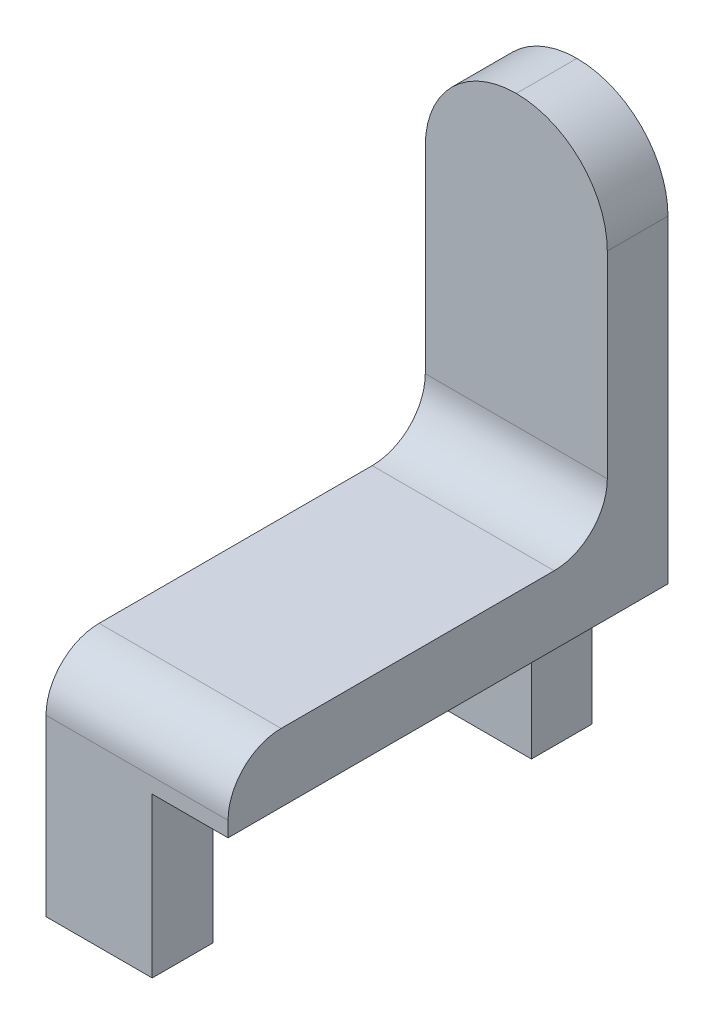
SolidWorks part; units mm, degrees
ref_plane "Front Plane" through (0, 0, 0) normal (0, 0, 1) x (1, 0, 0)
ref_plane "Top Plane" through (0, 0, 0) normal (0, 1, 0) x (1, 0, 0)
ref_plane "Right Plane" through (0, 0, 0) normal (1, 0, 0) x (0, 0, -1)
sketch "Sketch2" plane through (0, -0.0002, -27.9978) normal (0, 0, -1) x (1, 0, 0)
  line L1 (45.1952, -27.127) -> (69.1952, -27.127)
  line L2 (45.1952, -27.127) -> (45.1952, 47.873)
  line L3 (45.1952, 47.873) -> (69.1952, 47.873)
  line L4 (69.1952, -27.127) -> (69.1952, 47.873)
  dimension "D4" = 75
extrude "Boss-Extrude1" add sketch "Sketch2" along normal blind 8
fillet "Fillet1" radius 12 2 edges at (45.1952, 27.1268, -31.9981) (69.1952, 27.1268, -31.9981)
sketch "Sketch3" plane through (0, -0.0002, -27.9978) normal (0, 0, 1) x (1, 0, 0)
  line L0 (69.1952, 15.127) -> (69.1952, -47.873) construction
  line L1 (45.1952, -47.873) -> (69.1952, -47.873)
  line L2 (45.1952, -47.873) -> (45.1952, -17.873)
  line L3 (45.1952, -17.873) -> (69.1952, -17.873)
  line L4 (69.1952, -47.873) -> (69.1952, -17.873)
  dimension "D1" = 30
extrude "Boss-Extrude2" add sketch "Sketch3" along normal blind 50
sketch "Sketch4" plane through (69.1952, 0, 0) normal (1, 0, 0) x (0, 0, -1)
  line L2 (27.9977, -54.1007) -> (27.9977, -26.8732)
  line L3 (27.9977, -26.8732) -> (-14.0023, -26.8732)
  line L4 (-14.0023, -54.1007) -> (-14.0023, -26.8732)
  line L5 (-22.0023, -17.8728) -> (35.9977, -17.8728) construction
  line L6 (35.998, 15.1267) -> (35.9975, -47.8733) construction
  line L7 (6.9977, -17.8728) -> (6.9977, -54.1007) construction
  line L8 (27.9977, -54.1007) -> (-14.0023, -54.1007)
  dimension "D1" = 21
  dimension "D2" = 42
extrude "Cut-Extrude1" cut sketch "Sketch4" against normal up to surface (24 mm away) up to face at (45.1952, -16.8731, -13.9977)
fillet "Fillet2" radius 7 2 edges at (57.1952, -17.8728, 22.0023) (57.1952, -17.8732, -27.9977)
sketch "Sketch5" plane through (69.1952, 0, 0) normal (1, 0, 0) x (0, 0, -1)
  line L10 (-22.0025, -47.8728) -> (-22.0024, -24.8728) construction
  line L11 (35.998, 15.1267) -> (35.9975, -47.8733) construction
  line L20 (20.9977, -17.8732) -> (-15.0023, -17.8729)
  line L21 (-22.0024, -24.8728) -> (-22.0025, -47.8728)
  line L22 (-22.0025, -47.8728) -> (-14.0023, -47.8729)
  line L23 (-14.0023, -47.8729) -> (-14.0023, -26.8732)
  line L24 (-14.0023, -26.8732) -> (27.9977, -26.8732)
  line L25 (27.9977, -26.8732) -> (27.9977, -47.8732)
  line L26 (27.9977, -47.8732) -> (35.9975, -47.8733)
  line L27 (35.9975, -47.8733) -> (35.998, 15.1267)
  line L28 (35.998, 15.1267) -> (27.998, 15.1268)
  line L29 (27.998, 15.1268) -> (27.9978, -10.8732)
  line L31 (-22.0024, -26.8732) -> (-22.0025, -47.8728)
  line L32 (-22.0025, -47.8728) -> (35.9975, -47.8733)
  line L34 (-22.0024, -26.8732) -> (35.9976, -26.8732)
  line L37 (35.9975, -47.8733) -> (35.9976, -26.8732)
  arc A2 (-15.0023, -17.8729) -> (-22.0024, -24.8728) centre (-15.0024, -24.8729) ccw
  arc A3 (20.9977, -17.8732) -> (27.9978, -10.8732) centre (20.9978, -10.8732) ccw
  point P2 (0, 0)
  point P8 (35.479, -47.8733)
  point P9 (-22.0024, -26.8732)
  point P18 (35.9976, -26.8732)
  dimension "D1" = 0
extrude "Cut-Extrude3" cut sketch "Sketch5" against normal blind 10
